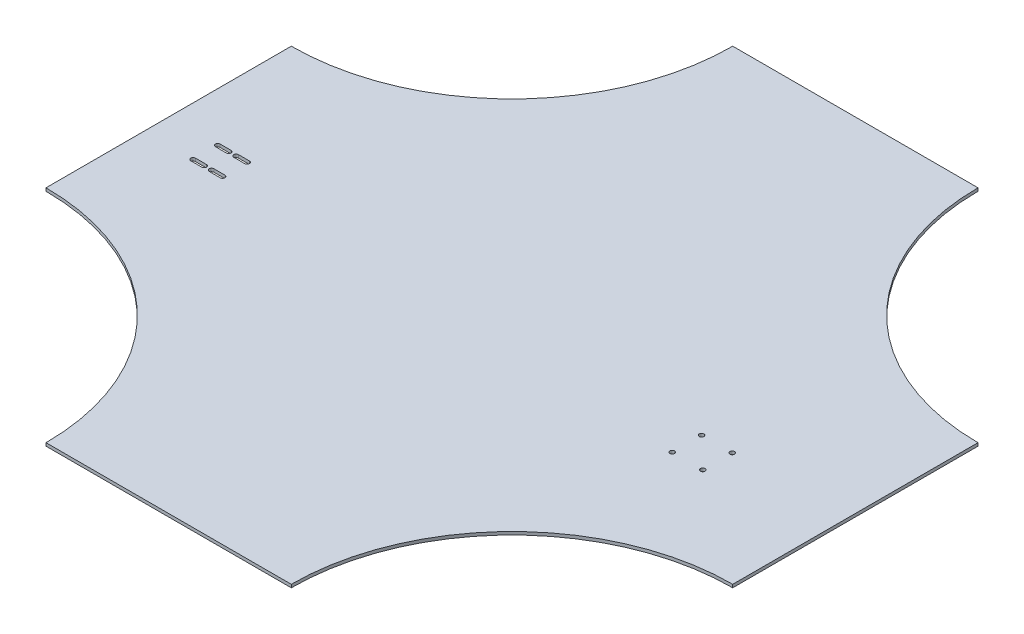
SolidWorks part; units mm, degrees
material "6061 Alloy"
ref_plane "Front Plane" through (0, 0, 0) normal (0, 0, 1) x (1, 0, 0)
ref_plane "Top Plane" through (0, 0, 0) normal (0, 1, 0) x (1, 0, 0)
ref_plane "Right Plane" through (0, 0, 0) normal (1, 0, 0) x (0, 0, -1)
sketch "Sketch1" plane through (0, 0, 0) normal (0, 1, 0) x (1, 0, 0)
  line L9 (-127, -355.6) -> (127, -355.6)
  line L10 (-355.6, -127) -> (-355.6, 127)
  line L11 (-127, 355.6) -> (127, 355.6)
  line L12 (355.6, -127) -> (355.6, 127)
  line L13 (-193.9554, -193.9554) -> (193.9554, 193.9554) construction
  line L14 (-193.9554, 193.9554) -> (193.9554, -193.9554) construction
  arc A8 (-355.6, 127) -> (-127, 355.6) centre (-355.6, 355.6) ccw
  arc A9 (127, 355.6) -> (355.6, 127) centre (355.6, 355.6) ccw
  arc A10 (355.6, -127) -> (127, -355.6) centre (355.6, -355.6) ccw
  arc A11 (-127, -355.6) -> (-355.6, -127) centre (-355.6, -355.6) ccw
  point P0 (0, 0)
  point P1 (0, 0)
  point P2 (0, 0)
  dimension "D3" = 457.2
  dimension "D4" = 457.2
  dimension "D5" = 457.2
  dimension "D6" = 457.2
  dimension "D1" = 711.2
  dimension "D2" = 711.2
extrude "Boss-Extrude1" add sketch "Sketch1" along normal blind 3.175
sketch "Sketch2" plane through (0, 3.175, 0) normal (0, 1, 0) x (1, 0, 0)
  line L0 (-304.8, 2.413) -> (-293.37, 2.413)
  line L1 (-304.8, -22.987) -> (-293.37, -22.987)
  line L2 (-293.37, -2.413) -> (-304.8, -2.413)
  line L3 (-285.75, -2.413) -> (-274.32, -2.413)
  line L4 (-285.75, -22.987) -> (-274.32, -22.987)
  line L5 (-274.32, 2.413) -> (-285.75, 2.413)
  line L6 (-293.37, -27.813) -> (-304.8, -27.813)
  line L7 (-355.6, 127) -> (-355.6, -127) construction
  line L8 (-274.32, -27.813) -> (-285.75, -27.813)
  arc A0 (-293.37, -2.413) -> (-293.37, 2.413) centre (-293.37, 0) ccw
  arc A1 (-274.32, -2.413) -> (-274.32, 2.413) centre (-274.32, 0) ccw
  arc A2 (-274.32, -27.813) -> (-274.32, -22.987) centre (-274.32, -25.4) ccw
  arc A3 (-293.37, -27.813) -> (-293.37, -22.987) centre (-293.37, -25.4) ccw
  arc A4 (-285.75, 2.413) -> (-285.75, -2.413) centre (-285.75, 0) ccw
  arc A5 (-304.8, 2.413) -> (-304.8, -2.413) centre (-304.8, 0) ccw
  arc A6 (-304.8, -22.987) -> (-304.8, -27.813) centre (-304.8, -25.4) ccw
  arc A7 (-285.75, -22.987) -> (-285.75, -27.813) centre (-285.75, -25.4) ccw
  dimension "D1" = 4.826
  dimension "D2" = 4.826
  dimension "D3" = 4.826
  dimension "D4" = 4.826
  dimension "D5" = 4.826
  dimension "D6" = 4.826
  dimension "D7" = 4.826
  dimension "D8" = 4.826
  dimension "D9" = 11.43
  dimension "D10" = 11.43
  dimension "D11" = 11.43
  dimension "D12" = 11.43
  dimension "D13" = 19.05
  dimension "D14" = 19.05
  dimension "D15" = 25.4
  dimension "D16" = 25.4
  dimension "D17" = 0
  dimension "D18" = 50.8
extrude "Cut-Extrude1" cut sketch "Sketch2" against normal through all both and the other way through all
sketch "Sketch4" plane through (0, 3.175, 0) normal (0, 1, 0) x (1, 0, 0)
  circle A0 centre (237.49, -9.4302) radius 2.413
  circle A1 centre (205.74, -9.4302) radius 2.413
  circle A2 centre (237.49, -39.9102) radius 2.413
  circle A3 centre (205.74, -39.9102) radius 2.413
extrude "Cut-Extrude2" cut sketch "Sketch4" against normal through all
